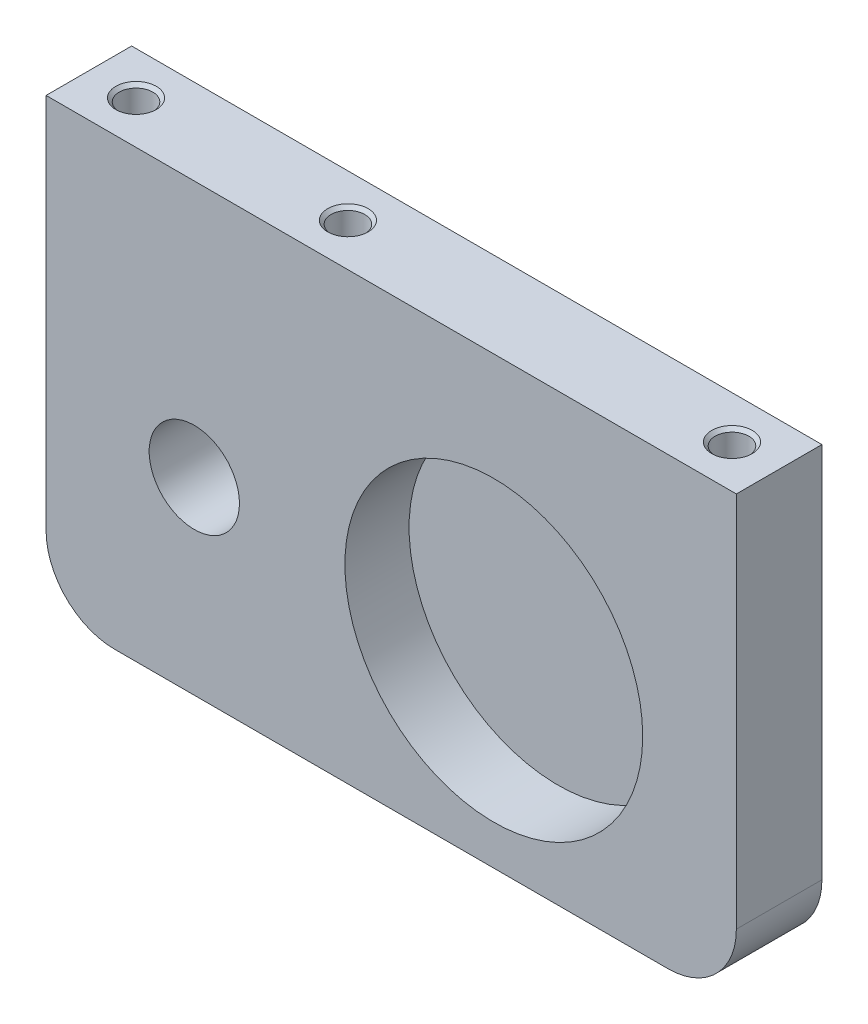
SolidWorks part; units mm, degrees
ref_plane "Front Plane" through (0, 0, 0) normal (0, 0, 1) x (1, 0, 0)
ref_plane "Top Plane" through (0, 0, 0) normal (0, 1, 0) x (1, 0, 0)
ref_plane "Right Plane" through (0, 0, 0) normal (1, 0, 0) x (0, 0, -1)
sketch "Sketch1" plane through (0, 0, 0) normal (0, 0, 1) x (1, 0, 0)
  line L10 (-33.225, 19.05) -> (18, 19.05)
  line L11 (-33.225, 19.05) -> (-33.225, -14)
  line L12 (-33.225, -14) -> (18, -14)
  line L13 (18, 19.05) -> (18, -14)
  circle A2 centre (0, 0) radius 11.05 construction
  circle A3 centre (-22.225, 0) radius 3.35 construction
  dimension "D2" = 6.7
  dimension "D5" = 19.05
  dimension "D6" = 11
  dimension "D3" = 22.225
  dimension "D1" = 22.1
  dimension "D8" = 51.225
  dimension "D4" = 14
  dimension "D7" = 18
extrude "Boss-Extrude1" add sketch "Sketch1" against normal blind 6.35
sketch "Sketch8" plane through (0, 19.05, 0) normal (0, 1, 0) x (1, 0, 0)
  line L0 (-33.225, 3.175) -> (18, 3.175) construction
  line L1 (-33.225, 6.35) -> (-33.225, 0) construction
  line L2 (18, 6.35) -> (18, 0) construction
  circle A1 centre (-29.725, 3.175) radius 1.25
  circle A2 centre (-14, 3.175) radius 1.25
  circle A3 centre (14.5, 3.175) radius 1.25
  dimension "D1" = 2.5
  dimension "D2" = 3.5
  dimension "D3" = 3.5
  dimension "D4" = 14
extrude "Cut-Extrude4" cut sketch "Sketch8" against normal blind 15
sketch "Sketch10" plane through (0, 0, 0) normal (0, 0, 1) x (1, 0, 0)
  circle A0 centre (-22.225, 0) radius 3.35 construction
  circle A1 centre (0, 0) radius 11.05 construction
  circle A2 centre (-22.225, 0) radius 3.35
  circle A3 centre (0, 0) radius 11.05
extrude "Cut-Extrude5" cut sketch "Sketch10" against normal offset from surface (4.7625 mm away) 1.5875 up to face at (-7.6125, 2.525, -6.35)
fillet "Fillet3" radius 5.08 2 edges at (18, -14, -3.175) (-33.225, -14, -3.175)
chamfer "Chamfer1" distance 0.25 angle 45 3 edges at (14.5, 19.05, -1.925) (-14, 19.05, -1.925) (-29.725, 19.05, -1.925)
